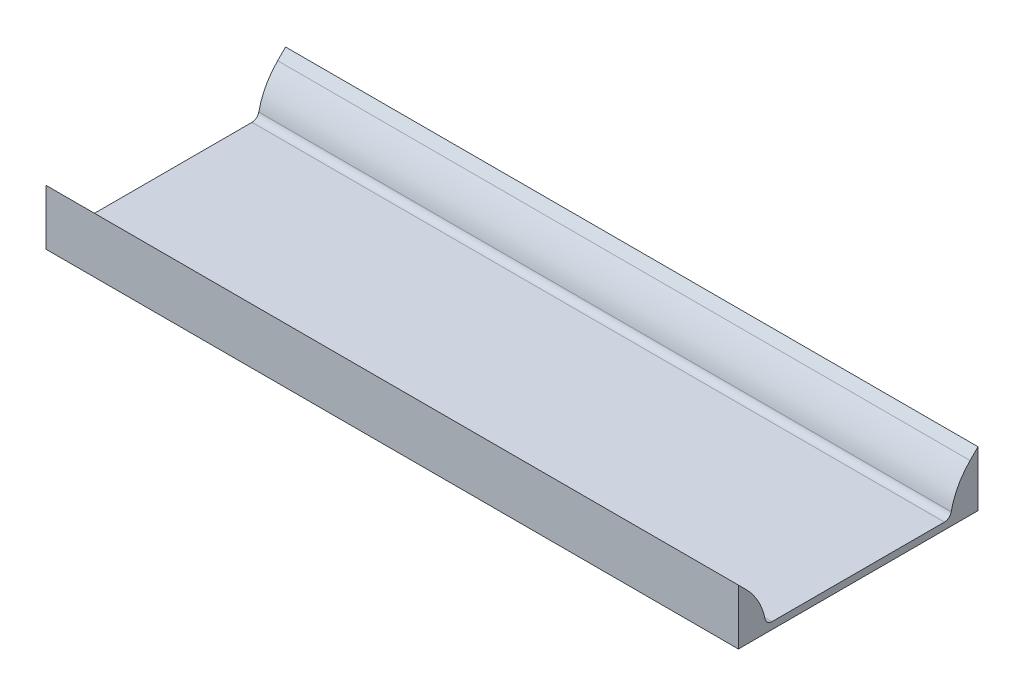
SolidWorks part; units mm, degrees
ref_plane "Front Plane" through (0, 0, 0) normal (0, 0, 1) x (1, 0, 0)
ref_plane "Top Plane" through (0, 0, 0) normal (0, 1, 0) x (1, 0, 0)
ref_plane "Right Plane" through (0, 0, 0) normal (1, 0, 0) x (0, 0, -1)
sketch "Sketch1" plane through (0, 0, 0) normal (0, 1, 0) x (1, 0, 0)
  line L1 (-63.5, 21.971) -> (63.5, 21.971)
  line L2 (-63.5, 21.971) -> (-63.5, -21.971)
  line L3 (-63.5, -21.971) -> (63.5, -21.971)
  line L4 (63.5, 21.971) -> (63.5, -21.971)
  line L5 (-63.5, 21.971) -> (63.5, -21.971) construction
  line L6 (-63.5, -21.971) -> (63.5, 21.971) construction
  point P0 (0, 0)
  dimension "D1" = 43.942
  dimension "D2" = 127
extrude "Boss-Extrude1" add sketch "Sketch1" along normal blind 10.16
sketch "Sketch2" plane through (0, 10.16, 0) normal (0, 1, 0) x (1, 0, 0)
  line L0 (63.5, -21.971) -> (63.5, 21.971) construction
  line L1 (-57.15, 16.891) -> (57.15, 16.891)
  line L2 (-57.15, 16.891) -> (-57.15, -16.891)
  line L3 (-57.15, -16.891) -> (57.15, -16.891)
  line L4 (57.15, 16.891) -> (57.15, -16.891)
  line L5 (-57.15, 16.891) -> (57.15, -16.891) construction
  line L6 (-57.15, -16.891) -> (57.15, 16.891) construction
  line L7 (63.5, 21.971) -> (-63.5, 21.971) construction
  line L8 (-63.5, 21.971) -> (-63.5, -21.971) construction
  line L9 (57.15, 16.891) -> (63.5, 16.891)
  line L10 (57.15, 16.891) -> (57.15, -16.891)
  line L11 (57.15, -16.891) -> (63.5, -16.891)
  line L12 (63.5, 16.891) -> (63.5, -16.891)
  line L13 (-57.15, 16.891) -> (-63.5, 16.891)
  line L14 (-57.15, 16.891) -> (-57.15, -16.891)
  line L15 (-57.15, -16.891) -> (-63.5, -16.891)
  line L16 (-63.5, 16.891) -> (-63.5, -16.891)
  point P0 (0, 0)
  line M5 (63.5, -21.971) -> (63.5, 21.971)
  line M7 (-63.5, 21.971) -> (-63.5, -21.971)
  dimension "D1" = 6.35
  dimension "D2" = 5.08
extrude "Cut-Extrude1" cut sketch "Sketch2" against normal blind 8.89 contours L4 L1 L2 L3 | L4 L11 L9 M5 | L15 L2 L13 M7 region at (0, 10.16, 0) region at (-60.325, 10.16, 0) region at (60.325, 10.16, 0)
chamfer "Chamfer1" distance 5.08 angle 45 2 edges at (0, 10.16, 16.891) (0, 10.16, -16.891)
fillet "Fillet1" radius 12.7 2 edges at (0, 5.08, 16.891) (0, 5.08, -16.891)
sketch "Sketch3" plane through (0, 0, 21.971) normal (0, 0, 1) x (1, 0, 0)
  line L0 (-63.5, 0) -> (63.5, 0)
  line L1 (-63.5, 0) -> (-63.5, 5.08)
  line L2 (-63.5, 10.16) -> (-63.5, 0) construction
  line L3 (63.5, 0) -> (63.5, 4.4369)
  line L4 (63.5, 10.16) -> (63.5, 0) construction
  point P4 (69.85, 2.1976)
  point P8 (-63.6764, 4.9173)
  point P9 (63.8171, 4.7386)
  point P13 (63.5, -53.3927)
  dimension "D1" = 5.08
extrude "Boss-Extrude2" [suppressed] add sketch "Sketch3" against normal blind 43.18
fillet "Fillet2" radius 1.27 2 edges at (0, 1.27, 16.891) (0, 1.27, -16.891)
